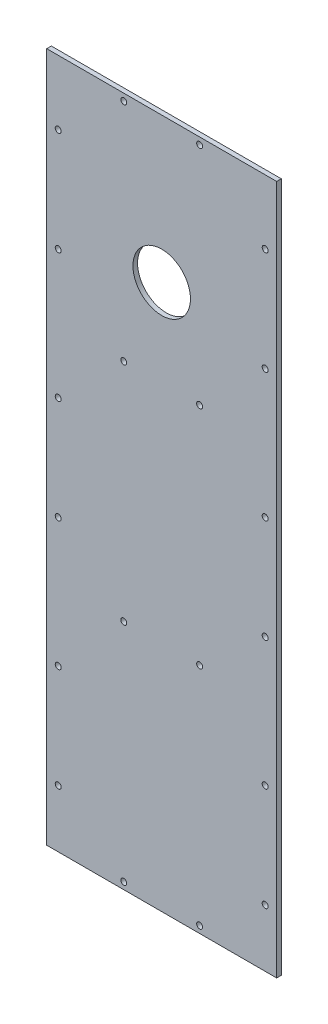
SolidWorks part; units mm, degrees
material "Alumina"
ref_plane "Front Plane" through (0, 0, 0) normal (0, 0, 1) x (1, 0, 0)
ref_plane "Top Plane" through (0, 0, 0) normal (0, 1, 0) x (1, 0, 0)
ref_plane "Right Plane" through (0, 0, 0) normal (1, 0, 0) x (0, 0, -1)
sketch "Sketch1" plane through (0, 0, 0) normal (0, 0, 1) x (1, 0, 0)
  line L1 (50, -150) -> (-50, -150)
  line L2 (50, -150) -> (50, 150)
  line L3 (50, 150) -> (-50, 150)
  line L4 (-50, -150) -> (-50, 150)
  line L5 (50, -150) -> (-50, 150) construction
  line L6 (50, 150) -> (-50, -150) construction
  point P0 (0, 0)
  dimension "D1" = 100
  dimension "D2" = 300
extrude "Boss-Extrude1" add sketch "Sketch1" along normal blind 2
sketch "Sketch2" plane through (0, 0, 2) normal (0, 0, 1) x (1, 0, 0)
  line L0 (-50, 150) -> (-50, -150) construction
  line L1 (50, 150) -> (-50, 150) construction
  line L2 (-50, -150) -> (50, -150) construction
  line L4 (0, -1.1) -> (0, 1.1) construction
  line L5 (-45, 122) -> (-45, 21) construction
  circle A0 centre (-45, 122) radius 1.3
  circle A1 centre (-45, 77) radius 1.3
  circle A2 centre (45, 122) radius 1.3
  circle A3 centre (45, 77) radius 1.3
  circle A4 centre (-45, 21) radius 1.3
  circle A5 centre (-45, -24) radius 1.3
  circle A6 centre (45, 21) radius 1.3
  circle A7 centre (45, -24) radius 1.3
  circle A8 centre (-45, -80) radius 1.3
  circle A9 centre (-45, -125) radius 1.3
  circle A10 centre (45, -80) radius 1.3
  circle A11 centre (45, -125) radius 1.3
  circle A13 centre (16.5, -147) radius 1.3
  circle A14 centre (-16.5, -147) radius 1.3
  circle A15 centre (-16.5, -49) radius 1.3
  circle A16 centre (16.5, -49) radius 1.3
  circle A17 centre (-16.5, 49) radius 1.3
  circle A18 centre (16.5, 49) radius 1.3
  circle A19 centre (-16.5, 147) radius 1.3
  circle A20 centre (16.5, 147) radius 1.3
  dimension "D1" = 2.6
  dimension "D3" = 28
  dimension "D4" = 2.6
  dimension "D6" = 5
  dimension "D10" = 2.6
  dimension "D11" = 33
  dimension "D13" = 3
  dimension "D14" = 90
  dimension "D15" = 5
  dimension "D16" = 3
  dimension "D2" = 5
  dimension "D9" = 25
  dimension "D17" = 101
  dimension "D7" = 2
  dimension "D8" = 3
  dimension "D12" = 4
extrude "Cut-Extrude1" cut sketch "Sketch2" against normal blind 10
sketch "Sketch3" plane through (0, 0, 0) normal (0, 0, -1) x (-1, 0, 0)
  line L0 (-50, 150) -> (50, 150) construction
  line L1 (-50, -150) -> (-50, 150) construction
  circle A0 centre (0, 87) radius 12.5
  dimension "D2" = 25
  dimension "D3" = 50
  dimension "D1" = 63
extrude "Cut-Extrude2" cut sketch "Sketch3" against normal blind 10
